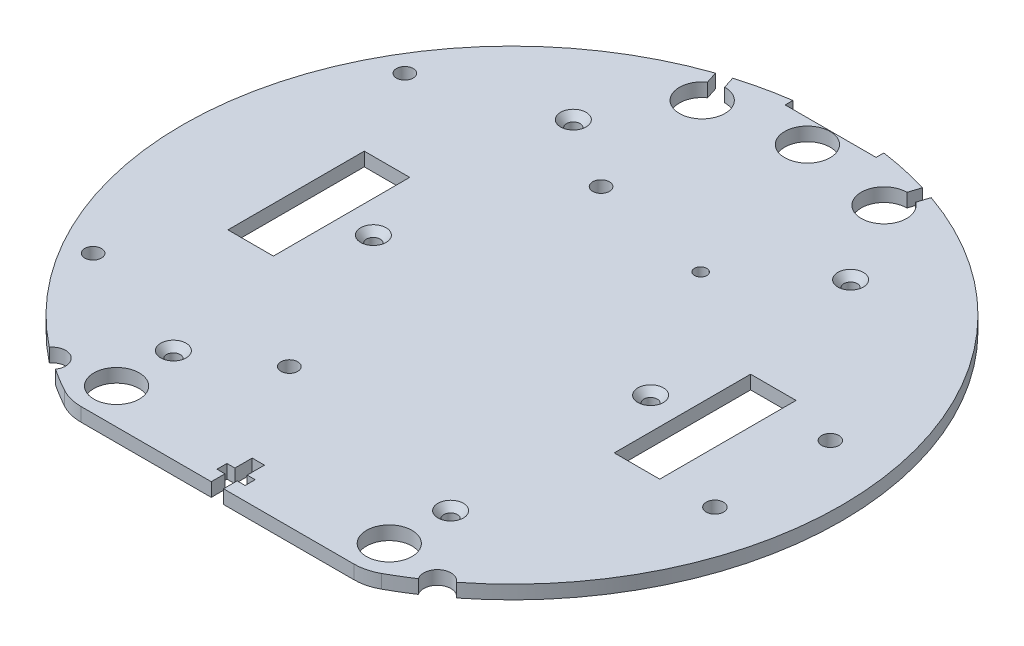
SolidWorks part; units mm, degrees
material "ABS"
ref_plane "Front Plane" through (0, 0, 0) normal (0, 0, 1) x (1, 0, 0)
ref_plane "Top Plane" through (0, 0, 0) normal (0, 1, 0) x (1, 0, 0)
ref_plane "Right Plane" through (0, 0, 0) normal (1, 0, 0) x (0, 0, -1)
sketch "Sketch1" plane through (0, 0, 0) normal (0, 1, 0) x (1, 0, 0)
  line L0 (0, -85) -> (0, 0) construction
  line L1 (30.03, -64.8129) -> (-30.03, -64.8129)
  arc A0 (34.8348, -63.5829) -> (-34.8348, -63.5829) centre (0, 0) ccw
  circle A1 centre (0, -85) radius 38.25 construction
  arc A2 (30.03, -64.8129) -> (34.8348, -63.5829) centre (30.03, -54.8129) ccw
  arc A3 (-30.03, -64.8129) -> (-34.8348, -63.5829) centre (-30.03, -54.8129) cw
  point P12 (-32.4891, -64.8129)
  dimension "D1" = 145
  dimension "D3" = 76.5
  dimension "D4" = 10
  dimension "D2" = 85
extrude "Boss-Extrude1" add sketch "Sketch1" along normal blind 3
sketch "Sketch2" plane through (0, 3, 0) normal (0, 1, 0) x (1, 0, 0)
  line L1 (-30.5, -44) -> (30.5, -44) construction
  line L2 (-30.5, -44) -> (-30.5, 44) construction
  line L3 (-30.5, 44) -> (30.5, 44) construction
  line L4 (30.5, -44) -> (30.5, 44) construction
  line L5 (-30.5, -44) -> (30.5, 44) construction
  line L6 (-30.5, 44) -> (30.5, -44) construction
  circle A0 centre (-30.5, 44) radius 1.5
  circle A1 centre (30.5, 44) radius 1.5
  circle A2 centre (30.5, 0) radius 1.5
  circle A3 centre (30.5, -44) radius 1.5
  circle A4 centre (-30.5, -44) radius 1.5
  circle A5 centre (-30.5, 0) radius 1.5
  point P0 (0, 0)
  dimension "D3" = 3
  dimension "D1" = 61
  dimension "D2" = 88
extrude "Cut-Extrude1" cut sketch "Sketch2" against normal through all
chamfer "Chamfer1" distance 1.5 angle 41 6 edges at (30.5, 3, -42.5) (30.5, 3, 1.5) (30.5, 3, 45.5) (-30.5, 3, 45.5) (-30.5, 3, 1.5) (-30.5, 3, -42.5) first distance on face at (30.5, 0, -42.5) first distance on face at (30.5, 0, 1.5) first distance on face at (30.5, 0, 45.5) first distance on face at (-30.5, 0, 45.5) first distance on face at (-30.5, 0, 1.5) first distance on face at (-30.5, 0, -42.5)
sketch "Sketch3" plane through (0, 3, 0) normal (0, 1, 0) x (1, 0, 0)
  line L0 (-30.03, -64.8129) -> (30.03, -64.8129) construction
  line L1 (1.35, -61.8129) -> (3.1, -61.8129)
  line L2 (-3.1, -59.6129) -> (-1.35, -59.6129)
  line L3 (-3.1, -59.6129) -> (-3.1, -61.8129)
  line L4 (-3.1, -61.8129) -> (-1.35, -61.8129)
  line L5 (3.1, -59.6129) -> (3.1, -61.8129)
  line L6 (-1.35, -64.8129) -> (1.35, -64.8129)
  line L7 (-1.35, -64.8129) -> (-1.35, -61.8129)
  line L8 (1.35, -59.6129) -> (3.1, -59.6129)
  line L9 (1.35, -64.8129) -> (1.35, -61.8129)
  line L11 (-1.35, -59.6129) -> (-1.35, -55.8129)
  line L12 (-1.35, -55.8129) -> (1.35, -55.8129)
  line L13 (1.35, -59.6129) -> (1.35, -55.8129)
  point P10 (0, -64.8129)
  point P14 (0, -64.8129)
  dimension "D1" = 2.7
  dimension "D2" = 6.2
  dimension "D3" = 2.2
  dimension "D4" = 3
  dimension "D5" = 9
extrude "Cut-Extrude2" cut sketch "Sketch3" against normal through all
sketch "Sketch4" plane through (0, 3, 0) normal (0, 1, 0) x (1, 0, 0)
  line L1 (-10, 71.807) -> (10, 71.807)
  line L2 (-10, 71.807) -> (-10, 70.107)
  line L3 (-10, 70.107) -> (10, 70.107)
  line L4 (10, 71.807) -> (10, 70.107)
  arc A0 (34.8348, -63.5829) -> (-34.8348, -63.5829) centre (0, 0) ccw construction
  dimension "D1" = 1.7
  dimension "D2" = 20
extrude "Cut-Extrude3" cut sketch "Sketch4" against normal through all
sketch "Sketch5" plane through (0, 3, 0) normal (0, 1, 0) x (1, 0, 0)
  line L0 (0, 0) -> (0, 65) construction
  circle A0 centre (0, 65) radius 5
  circle A1 centre (30, -57) radius 5
  circle A2 centre (-30, -57) radius 5
  dimension "D1" = 10
  dimension "D2" = 65
  dimension "D3" = 57
  dimension "D4" = 30
extrude "Cut-Extrude4" cut sketch "Sketch5" against normal through all
sketch "Sketch6" plane through (0, 3, 0) normal (0, 1, 0) x (1, 0, 0)
  line L0 (-10.8818, -38.1) -> (-10.8818, 38.1) construction
  line L1 (-57.8718, -34.29) -> (-14.6918, -34.29) construction
  line L2 (-57.8718, -34.29) -> (-57.8718, 34.29) construction
  line L3 (-57.8718, 34.29) -> (-14.6918, 34.29) construction
  line L4 (-14.6918, -34.29) -> (-14.6918, 34.29) construction
  line L5 (-61.6818, 38.1) -> (-10.8818, 38.1) construction
  line L6 (-61.6818, -38.1) -> (-61.6818, 38.1) construction
  line L7 (-61.6818, -38.1) -> (-10.8818, -38.1) construction
  circle A0 centre (-57.8718, 34.29) radius 1.8415
  circle A1 centre (-57.8718, -34.29) radius 1.8415
  circle A2 centre (-14.6918, -34.29) radius 1.8415
  circle A3 centre (-14.6918, 34.29) radius 1.8415
  arc A5 (-10, 71.807) -> (-34.8348, -63.5829) centre (0, 0) ccw construction
  point P13 (-61.6818, 0)
  point P14 (0, 0)
  point P15 (-14.6918, 0)
  point P17 (-72.5, 0)
  dimension "D3" = 3.683
  dimension "D1" = 43.18
  dimension "D2" = 68.58
  dimension "D4" = 3.81
extrude "Cut-Extrude5" cut sketch "Sketch6" against normal through all
sketch "Sketch7" plane through (0, 3, 0) normal (0, 1, 0) x (1, 0, 0)
  circle A0 centre (12.5232, 28.985) radius 1.3716
  dimension "D1" = 2.7432
extrude "Cut-Extrude6" cut sketch "Sketch7" against normal through all
sketch "Sketch8" plane through (0, 3, 0) normal (0, 1, 0) x (1, 0, 0)
  line L0 (1.35, -64.8129) -> (30.03, -64.8129) construction
  line L1 (-20, 61.8466) -> (20, 61.8466) construction
  line L2 (-10, 70.107) -> (10, 70.107) construction
  line L3 (-37.5, 0) -> (37.5, 0) construction
  line L4 (-47.5, 15) -> (-37.5, 15)
  line L5 (-47.5, 15) -> (-47.5, -15)
  line L6 (-47.5, -15) -> (-37.5, -15)
  line L7 (-37.5, 15) -> (-37.5, -15)
  line L8 (37.5, 15) -> (47.5, 15)
  line L9 (37.5, 15) -> (37.5, -15)
  line L10 (37.5, -15) -> (47.5, -15)
  line L11 (47.5, 15) -> (47.5, -15)
  line L12 (-23.7301, 68.5064) -> (-22.8948, 65.9233)
  line L13 (-22.3029, 68.968) -> (-20, 61.8466) construction
  line L14 (-20.0404, 66.8464) -> (-20.8757, 69.4295)
  line L15 (20.0404, 66.8464) -> (20.8757, 69.4295)
  line L16 (22.3077, 68.9827) -> (20, 61.8466) construction
  line L17 (22.8948, 65.9233) -> (23.7301, 68.5064)
  line L18 (22.8948, 65.9233) -> (20.0404, 66.8464) construction
  line L19 (-22.8948, 65.9233) -> (-20.0404, 66.8464) construction
  arc A0 (39.9251, -60.5164) -> (44.7914, -57.0086) centre (42.3945, -58.8129) cw
  arc A1 (34.8348, -63.5829) -> (10, 71.807) centre (0, 0) ccw construction
  arc A2 (39.9251, -60.5164) -> (44.7914, -57.0086) centre (0, 0) ccw
  arc A3 (-39.9251, -60.5164) -> (-44.7914, -57.0086) centre (-42.3945, -58.8129) ccw
  arc A4 (-10, 71.807) -> (-34.8348, -63.5829) centre (0, 0) ccw construction
  arc A5 (-44.7914, -57.0086) -> (-39.9251, -60.5164) centre (0, 0) ccw
  circle A6 centre (58.9011, -14.2589) radius 1.905
  circle A7 centre (-20, 61.8466) radius 5 construction
  circle A8 centre (20, 61.8466) radius 5 construction
  circle A9 centre (0, 65) radius 5 construction
  arc A10 (-20, 61.8466) -> (20, 61.8466) centre (0, 0) cw construction
  arc A11 (-23.7301, 68.5064) -> (-20.8757, 69.4295) centre (-22.3029, 68.968) cw
  arc A12 (-22.8948, 65.9233) -> (-20.0404, 66.8464) centre (-20, 61.8466) ccw
  arc A13 (20.0404, 66.8464) -> (22.8948, 65.9233) centre (20, 61.8466) ccw
  arc A14 (20.8757, 69.4295) -> (23.7301, 68.5064) centre (22.3029, 68.968) cw
  circle A15 centre (58.9011, 11.1411) radius 1.905
  point P7 (40.6403, -56.3792)
  point P11 (0, 61.8466)
  point P12 (42.3945, -58.8129)
  point P24 (0, 70.107)
  point P27 (0, 65)
  point P37 (47.5, 0)
  point P38 (-37.5, 0)
  point P39 (37.5, 0)
  point P41 (0, 0)
  point P56 (21.4676, 66.3849)
  point P61 (0, 0)
  point P62 (0, 0)
  dimension "D8" = 3.81
  dimension "D1" = 3
  dimension "D2" = 6
  dimension "D3" = 40
  dimension "D4" = 10
  dimension "D5" = 30
  dimension "D6" = 75
  dimension "D7" = 3
extrude "Cut-Extrude7" cut sketch "Sketch8" against normal through all
equation "\"smallPulleyTeeth\"= 30"
equation "\"largePulleyTeeth\"= 30"
equation "\"eighthThick\"= 3.0mm"
equation "\"sixteenthThick\" = 1.7mm"
equation "\"quarterThick\"=6.0mm"
equation "\"OD\" = 145mm"
equation "\"puckAngle\" = 60.5deg"
equation "\"puckDiam\" = 76.5mm"
equation "\"puckDist\" = 85mm"
equation "\"scoopFillet\" = 5mm"
equation "\"axlePress\" = 5.9mm"
equation "\"press\" = 0.2mm"
equation "\"wheelClear\" = 0.3mm"
equation "\"10-32clear\" = 4.8mm"
equation "\"10-32tap\" = 4.45mm"
equation "\"6-32clear\" = 3.3mm"
equation "\"8-32clear\" = 4.0mm"
equation "\"4-40clear\" = 3.0mm"
equation "\"wheelHeight\" = 22mm"
equation "\"wheelWell\" = 65mm"
equation "\"ledSmall\" = 3.1mm"
equation "\"ledLarge\" = 4.2mm"
equation "\"ledLength\" = 4.2mm"
equation "\"D1@Sketch1\"=\"OD\""
equation "\"D1@Boss-Extrude1\"=\"eighthThick\""
equation "\"D3@Sketch2\"=\"4-40clear\""
equation "\"D3@Sketch1\"=\"puckDiam\""
equation "\"D2@Sketch1\"=\"puckDist\""
equation "\"4-40close\" = 2.7mm"
equation "\"4-40nutThick\" = 2.2mm"
equation "\"4-40nutWidth\" = 6.2mm"
equation "\"D1@Sketch4\"=\"sixteenthThick\""
equation "\"D1@Sketch3\"=\"4-40close\""
equation "\"4-40insertHeight\" = 3.5mm"
equation "\"4-40insert\" = 4.25mm"
equation "\"D2@Sketch3\"=\"4-40nutWidth\""
equation "\"D3@Sketch3\"=\"4-40nutThick\""
